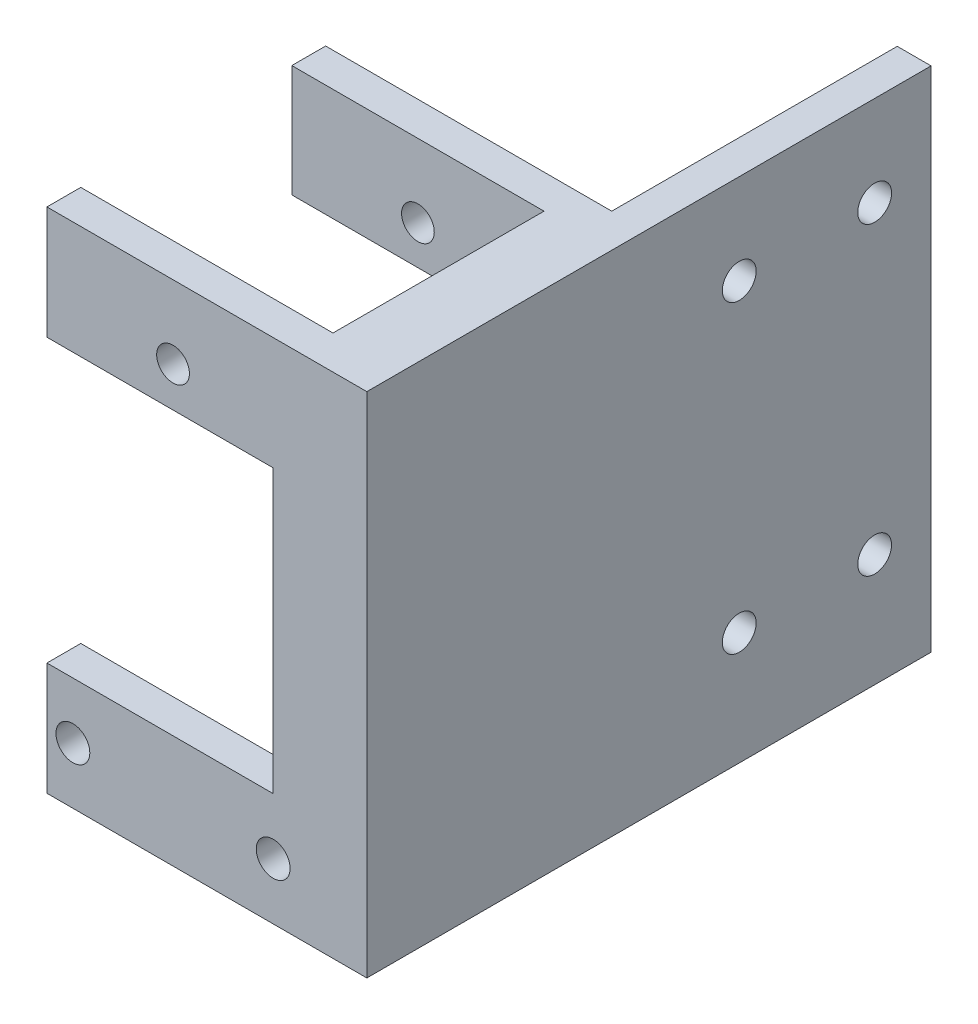
SolidWorks part; units mm, degrees
note: The reader was unsure of these and kept them because the rebuilt part matched: shared geometry of "Sketch8<3>".
ref_plane "Front Plane" through (0, 0, 0) normal (0, 0, 1) x (1, 0, 0)
ref_plane "Top Plane" through (0, 0, 0) normal (0, 1, 0) x (1, 0, 0)
ref_plane "Right Plane" through (0, 0, 0) normal (1, 0, 0) x (0, 0, -1)
sketch "Sketch2" plane through (0, 0, 0) normal (0, 0, 1) x (1, 0, 0)
  line L1 (12.675, -22.5) -> (-12.675, -22.5)
  line L2 (12.675, -22.5) -> (12.675, 22.5)
  line L3 (12.675, 22.5) -> (-12.675, 22.5)
  line L4 (-12.675, -22.5) -> (-12.675, 22.5)
  line L5 (12.675, -22.5) -> (-12.675, 22.5) construction
  line L6 (12.675, 22.5) -> (-12.675, -22.5) construction
  line L7 (-12.675, 22.5) -> (12.675, 22.5)
  line L8 (-12.675, 22.5) -> (-12.675, 12.5)
  line L9 (-12.675, 12.5) -> (12.675, 12.5)
  line L10 (12.675, 22.5) -> (12.675, 12.5)
  line L11 (-12.675, -22.5) -> (12.675, -22.5)
  line L12 (-12.675, -22.5) -> (-12.675, -12.5)
  line L13 (-12.675, -12.5) -> (12.675, -12.5)
  line L14 (12.675, -22.5) -> (12.675, -12.5)
  line L15 (12.675, 12.5) -> (7.375, 12.5)
  line L16 (12.675, 12.5) -> (12.675, -12.5)
  line L17 (12.675, -12.5) -> (7.375, -12.5)
  line L18 (7.375, 12.5) -> (7.375, -12.5)
  line L19 (-12.675, 12.5) -> (7.375, 12.5)
  line L20 (-12.675, 12.5) -> (-12.675, -12.5)
  line L21 (-12.675, -12.5) -> (7.375, -12.5)
  line L22 (7.375, 12.5) -> (7.375, -12.5)
  circle A2 centre (7.375, -17.5) radius 1.5
  circle A4 centre (-10.375, -17.5) radius 1.5
  circle A5 centre (-1.5, 16.025) radius 1.45
  point P0 (0, 0)
  dimension "D5" = 2.9
  dimension "D7" = 20.05
  dimension "D11" = 2.3
  dimension "D12" = 5
  dimension "D13" = 3
  dimension "D15" = 5
  dimension "D16" = 3
  dimension "D1" = 25.35
  dimension "D2" = 45
  dimension "D3" = 10
  dimension "D4" = 10
  dimension "D14" = 17.75
extrude "Boss-Extrude1" add sketch "Sketch2" against normal blind 3 contours L9 L18 L13 L2 | L4 L9 L2 L3 A5 | L13 L4 L1 L2 A4 A2
sketch "Sketch3" plane through (12.675, 0, 0) normal (1, 0, 0) x (0, 0, -1)
  line L1 (0, 22.5) -> (50, 22.5)
  line L2 (0, 22.5) -> (0, -22.5)
  line L3 (0, -22.5) -> (50, -22.5)
  line L4 (50, 22.5) -> (50, -22.5)
  dimension "D1" = 50
  dimension "D2" = 45
extrude "Boss-Extrude2" add sketch "Sketch3" along normal blind 3
sketch "Sketch7" plane through (0, 22.5, 0) normal (0, 1, 0) x (1, 0, 0)
  line L0 (15.675, 50) -> (15.675, 0) construction
  line L1 (15.675, 24.7) -> (-22.675, 24.7)
  line L2 (15.675, 24.7) -> (15.675, 21.7)
  line L3 (15.675, 21.7) -> (-22.675, 21.7)
  line L4 (-22.675, 24.7) -> (-22.675, 21.7)
  line L5 (12.675, 3) -> (-12.675, 3) construction
  dimension "D1" = 18.7
  dimension "D2" = 3
  dimension "D3" = 38.35
extrude "Boss-Extrude3" add sketch "Sketch7" against normal blind 45
sketch "Sketch8" plane through (0, 0, -21.7) normal (0, 0, 1) x (1, 0, 0)
  line L0 (15.675, 22.5) -> (15.675, -22.5) construction
  line L1 (-12.675, 22.5) -> (15.675, 22.5)
  line L2 (-12.675, 22.5) -> (-12.675, 12.5728)
  line L3 (-12.675, 12.5728) -> (15.675, 12.5728)
  line L4 (15.675, 22.5) -> (15.675, 12.5728)
  line L6 (-12.675, -12.5) -> (15.675, -12.5)
  line L7 (-12.675, -12.5) -> (-12.675, -22.5)
  line L8 (-12.675, -22.5) -> (15.675, -22.5)
  line L9 (15.675, -12.5) -> (15.675, -22.5)
  line L10 (7.375, -12.5) -> (15.675, -12.5)
  line L11 (7.375, -12.5) -> (7.375, 12.5728)
  line L12 (7.375, 12.5728) -> (15.675, 12.5728)
  line L13 (15.675, -12.5) -> (15.675, 12.5728)
  circle A1 centre (-10.375, -17.5) radius 1.5
  circle A2 centre (7.375, -17.5) radius 1.5
  circle A3 centre (-1.5, 16.025) radius 1.45
  line M3 (-22.675, 22.5) -> (-22.675, -22.5)
  dimension "D1" = 2.9
  dimension "D4" = 3
  dimension "D5" = 3
  dimension "D2" = 3.4522
  dimension "D3" = 17.75
extrude "Cut-Extrude1" cut sketch "Sketch8" against normal blind 5 contours L6 L11 L3 M3
extrude "Cut-Extrude2" cut sketch "Sketch8<3>" against normal blind 5 contours A3 | A2 | A1 | L6 L11 L3 M3
sketch "Sketch8<3>" plane through (0, 0, -21.7) normal (0, 0, 1) x (1, 0, 0) same geometry as "Sketch8"
sketch "Sketch11" plane through (15.675, 0, 0) normal (1, 0, 0) x (0, 0, -1)
  line L0 (0, -22.5) -> (50, -22.5) construction
  line L8 (50, -22.5) -> (50, 22.5) construction
  line L11 (50, 22.5) -> (0, 22.5) construction
  circle A4 centre (33, 14.5) radius 1.5
  circle A5 centre (45, 14.5) radius 1.5
  circle A6 centre (33, -12.5) radius 1.5
  circle A7 centre (45, -12.5) radius 1.5
  dimension "D2" = 5
  dimension "D3" = 8
  dimension "D4" = 27
  dimension "D5" = 5
  dimension "D7" = 3
  dimension "D6" = 8
  dimension "D8" = 3
  dimension "D9" = 3
  dimension "D10" = 3
  dimension "D11" = 12
  dimension "D12" = 12
  dimension "D13" = 10
extrude "Cut-Extrude4" cut sketch "Sketch11" against normal blind 5
sketch "Sketch12" plane through (12.675, 0, 0) normal (-1, 0, 0) x (0, 0, 1)
  line L1 (-21.7, 22.5) -> (-3, 22.5)
  line L2 (-21.7, 22.5) -> (-21.7, -22.5)
  line L3 (-21.7, -22.5) -> (-3, -22.5)
  line L4 (-3, 22.5) -> (-3, -22.5)
extrude "Boss-Extrude4" add sketch "Sketch12" along normal blind 3
